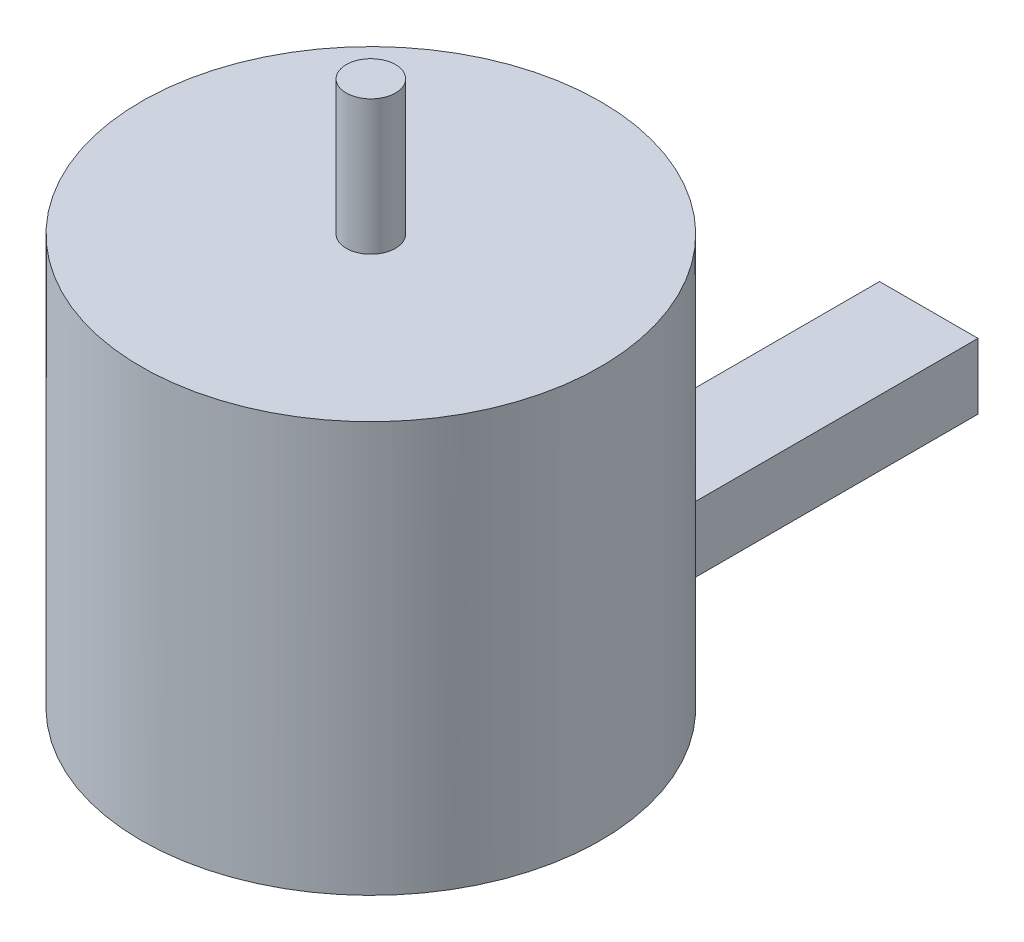
SolidWorks part; units mm, degrees
ref_plane "Front Plane" through (0, 0, 0) normal (0, 0, 1) x (1, 0, 0)
ref_plane "Top Plane" through (0, 0, 0) normal (0, 1, 0) x (1, 0, 0)
ref_plane "Right Plane" through (0, 0, 0) normal (1, 0, 0) x (0, 0, -1)
sketch "Sketch1" plane through (0, 0, 0) normal (0, 0, 1) x (1, 0, 0)
  line L0 (0, -74.46) -> (0, 71.5861) construction
  line L1 (-0.75, 0) -> (-7, 0)
  line L2 (55, 0) -> (-55, 0) construction
  line L3 (-7, 0) -> (-7, 12.5)
  line L4 (-7, 12.5) -> (-0.75, 12.5)
  line L5 (0, -0.9) -> (0, 16.6)
  line L6 (-0.75, 0) -> (-0.75, -0.9)
  line L7 (-0.75, 12.5) -> (-0.75, 16.6)
  line L8 (-0.75, 16.6) -> (0, 16.6)
  line L9 (-0.75, -0.9) -> (0, -0.9)
  dimension "D1" = 7
  dimension "D2" = 0.75
  dimension "D3" = 12.5
  dimension "D4" = 4.1
  dimension "D5" = 17.5
revolve "Revolve1" add sketch "Sketch1" angle 360 about L0
hole_wizard "M2x0.4 Tapped Hole1" positions "Sketch2" profile "Sketch3" tap size "M2x0.4" standard "ANSI Metric"
sketch "Sketch2" plane through (0, 0, 0) normal (0, -1, 0) x (-1, 0, 0)
  line L1 (-3.182, -3.182) -> (0, 0) construction
  line L2 (0, 0) -> (0, -2.9249) construction
  circle A0 centre (0, 0) radius 4.5
  point P0 (3.182, -3.182)
  point P11 (-3.182, -3.182)
  point P12 (-3.182, 3.182)
  point P13 (3.182, 3.182)
  dimension "D2" = 9
  dimension "D3" = 45
  dimension "D1" = 4
sketch "Sketch3" plane through (-3.182, 0, 3.182) normal (1, 0, 0) x (0, 0, -1)
  line L0 (0, 0) -> (0, 5.6807)
  line L1 (0, 5.6807) -> (0.8, 5.2)
  line L2 (0.8, 5.2) -> (0.8, 0)
  line L5 (0.8, 0) -> (0, 0)
  line L10 (0, 5.6807) -> (-0.8, 5.2) construction
  line L11 (0, -6.35) -> (0, 107.95) construction
  dimension "Tap Drill Dia." = 1.6
  dimension "Tap Drill Depth" = 5.2
  dimension "Drill Angle" = 118
cosmetic thread "Hole Thread1" parameters "D1"=4, "D2"=2
cosmetic thread "Hole Thread3" parameters "D1"=4, "D2"=2
cosmetic thread "Hole Thread4" parameters "D1"=4, "D2"=2
cosmetic thread "Hole Thread5" parameters "D1"=4, "D2"=2
ref_plane "Plane1" through (0, 0, -7) normal (0, 0, -1) x (-1, 0, 0)
sketch "Sketch4" plane through (0, 0, -7) normal (0, 0, -1) x (-1, 0, 0)
  line L1 (1.5, 0) -> (-1.5, 0)
  line L2 (1.5, 0) -> (1.5, 2)
  line L3 (1.5, 2) -> (-1.5, 2)
  line L4 (-1.5, 0) -> (-1.5, 2)
  point P4 (0, 0)
  dimension "D1" = 3
  dimension "D2" = 2
extrude "Boss-Extrude1" add sketch "Sketch4" along normal blind 10 and the other way blind 2
